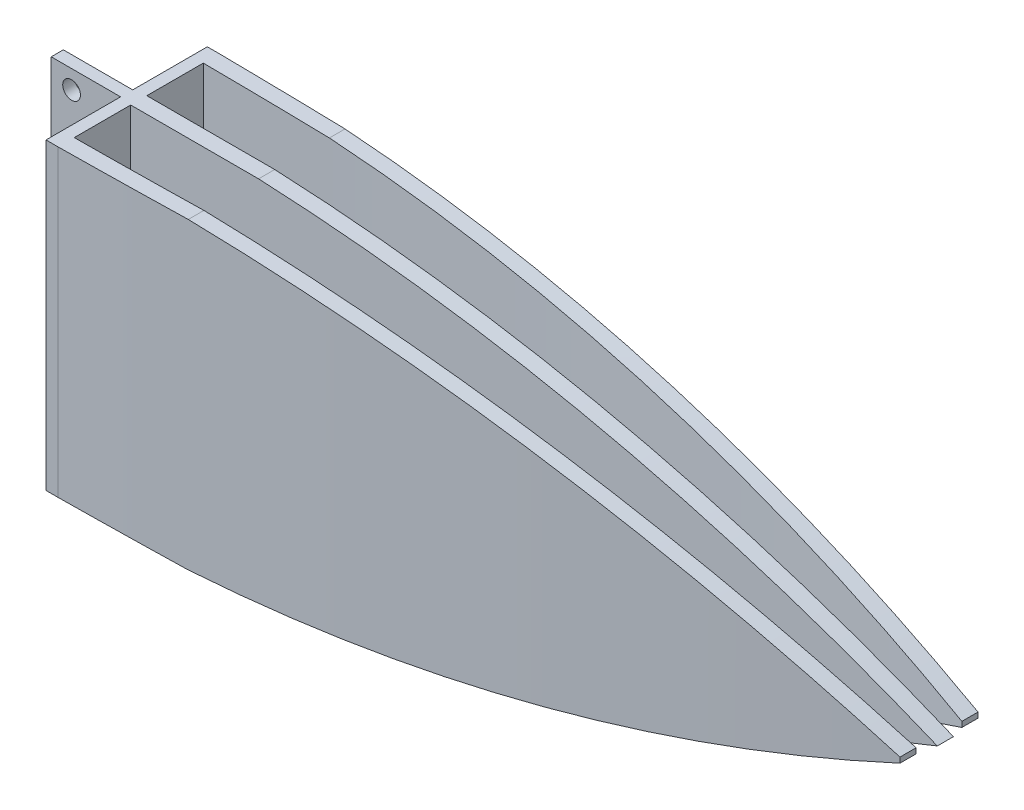
SolidWorks part; units mm, degrees
ref_plane "前基準面" through (0, 0, 0) normal (0, 0, 1) x (1, 0, 0)
ref_plane "上基準面" through (0, 0, 0) normal (0, 1, 0) x (1, 0, 0)
ref_plane "右基準面" through (0, 0, 0) normal (1, 0, 0) x (0, 0, -1)
sketch "草圖1" plane through (0, 0, 0) normal (0, 0, 1) x (1, 0, 0)
  line L0 (-6.5784, -18.2648) -> (-6.5784, 19.7352) construction
  line L4 (0.8982, 19.7352) -> (0.8982, -18.2648)
  line L13 (-4.1018, 17.2352) -> (-9.1018, 17.2352) construction
  line L14 (-4.1018, -15.7648) -> (-9.1018, -15.7648) construction
  line L16 (-9.1018, 19.7352) -> (0.8982, 19.7352)
  line L17 (-9.1018, -18.2648) -> (0.8982, -18.2648)
  line L18 (-9.1018, 19.7352) -> (-9.1018, -18.2648)
  circle A0 centre (-6.6018, -15.7648) radius 1.1
  circle A1 centre (-6.5784, 17.2352) radius 1.1
  dimension "D7" = 2.2
  dimension "D8" = 2.2
  dimension "D1" = 38
  dimension "D2" = 10
extrude "填料-伸長1" add sketch "草圖1" along normal blind 0.75 and the other way blind 0.75
ref_plane "平面1" through (-0.5, 0, 0) normal (1, 0, 0) x (0, 0, -1)
sketch "草圖3" plane through (-0.5, 0, 0) normal (1, 0, 0) x (0, 0, -1)
  line L0 (0, 19.7352) -> (0, -18.3016) construction
  line L1 (-10, 19.7352) -> (10, 19.7352)
  line L2 (-10, 19.7352) -> (-10, -18.3016)
  line L3 (-10, -18.3016) -> (10, -18.3016)
  line L4 (10, 19.7352) -> (10, -18.3016)
  line L5 (-0.75, -18.2648) -> (-0.75, 19.7352) construction
  line L6 (0.75, 19.7352) -> (-0.75, 19.7352) construction
  dimension "D1" = 0.75
  dimension "D2" = 10
  dimension "D3" = 0
extrude "填料-伸長2" add sketch "草圖3" along normal blind 1.5
sketch "草圖4" plane through (0, 0, 0) normal (0, 0, 1) x (1, 0, 0)
  line L2 (1, 19.7352) -> (1, -18.2989)
  line L5 (101, 0.7182) -> (1, 0.7182) construction
  arc A0 (1, 19.7352) -> (101, 0.7182) centre (5.8112, -227.3957) cw
  arc A1 (1, -18.2989) -> (101, 0.7182) centre (5.8112, 228.8321) ccw
  dimension "D1" = 100
extrude "填料-伸長3" add sketch "草圖4" along normal blind 1 and the other way blind 1
ref_plane "平面2" through (0, 19.7352, 0) normal (0, 1, 0) x (1, 0, 0)
sketch "草圖5" plane through (0, 19.7352, 0) normal (0, 1, 0) x (1, 0, 0)
  line L0 (1, -8) -> (1, -10)
  line L1 (1, -1) -> (1, -10) construction
  line L2 (100.2065, -2.8359) -> (100.2065, -4.8359)
  line L3 (1, 0) -> (101, 0) construction
  line L4 (1, 1) -> (1, -1) construction
  line L5 (101, 1) -> (101, -1) construction
  line L6 (100.2065, 2.8359) -> (100.2065, 4.8359)
  line L7 (1, 8) -> (1, 10)
  arc A0 (1, -8) -> (100.2065, -2.8359) centre (-6.3045, 1087.8166) ccw
  arc A1 (100.2065, -4.8359) -> (1, -10) centre (-12.8812, 1212.1599) cw
  arc A2 (1, 8) -> (100.2065, 2.8359) centre (-6.3045, -1087.8166) cw
  arc A3 (100.2065, 4.8359) -> (1, 10) centre (-12.8812, -1212.1599) ccw
  dimension "D2" = 2
  dimension "D1" = 2
  dimension "D3" = 2
extrude "填料-伸長4" add sketch "草圖5" against normal blind 38
ref_plane "平面3" through (0, 0, 10) normal (0, 0, 1) x (1, 0, 0)
sketch "草圖8" plane through (0, 0, 10) normal (0, 0, 1) x (1, 0, 0)
  line L1 (101, -18.2648) -> (101, 19.7011)
  line L2 (1, 0.7182) -> (101, 0.7182) construction
  line L3 (1, 19.7352) -> (1, -18.2989) construction
  line L4 (13.1037, 19.6745) -> (101, 19.7011)
  line L5 (13.1037, -18.2381) -> (101, -18.2648)
  arc A0 (13.1037, -18.2381) -> (101, 0.7182) centre (5.8112, 228.8321) ccw
  arc A1 (1, -18.2989) -> (101, 0.7182) centre (5.8112, 228.8321) ccw construction
  arc A2 (13.1037, 19.6745) -> (101, 0.7182) centre (5.8112, -227.3957) cw
extrude "除料-伸長1" cut sketch "草圖8" against normal blind 20 and the other way blind 10 contours A0 L5 L1 | L4 A2 L1 region at (77.7362, -12.5844, 10) region at (77.7362, 14.0208, 10)
ref_plane "平面4" through (0, 19.7352, 0) normal (0, 1, 0) x (1, 0, 0)
ref_plane "平面5" through (0, 19.7352, 0) normal (0, 1, 0) x (1, 0, 0)
sketch "草圖10" plane through (0, 19.7352, 0) normal (0, 1, 0) x (1, 0, 0)
  line L0 (-22.4534, -10) -> (22.4534, -10) construction
  line L1 (-9.7542, 10.5434) -> (102.7429, 10.5434)
  line L2 (-9.7542, 10.5434) -> (-9.7542, -10)
  line L3 (-9.7542, -10) -> (102.7429, -10)
  line L4 (102.7429, 10.5434) -> (102.7429, -10)
extrude "除料-伸長4" cut sketch "草圖10" against normal blind 0.2 and the other way blind 0.2
ref_plane "平面6" through (0, -18.3016, 0) normal (0, -1, 0) x (-1, 0, 0)
sketch "草圖11" plane through (0, -18.3016, 0) normal (0, -1, 0) x (-1, 0, 0)
  line L0 (-22.4534, -10) -> (22.4534, -10) construction
  line L1 (0.716, -10) -> (-103.7986, -10)
  line L2 (0.716, -10) -> (0.716, 11.6577)
  line L3 (0.716, 11.6577) -> (-103.7986, 11.6577)
  line L4 (-103.7986, -10) -> (-103.7986, 11.6577)
extrude "除料-伸長5" cut sketch "草圖11" against normal blind 0.2 and the other way blind 0.2
